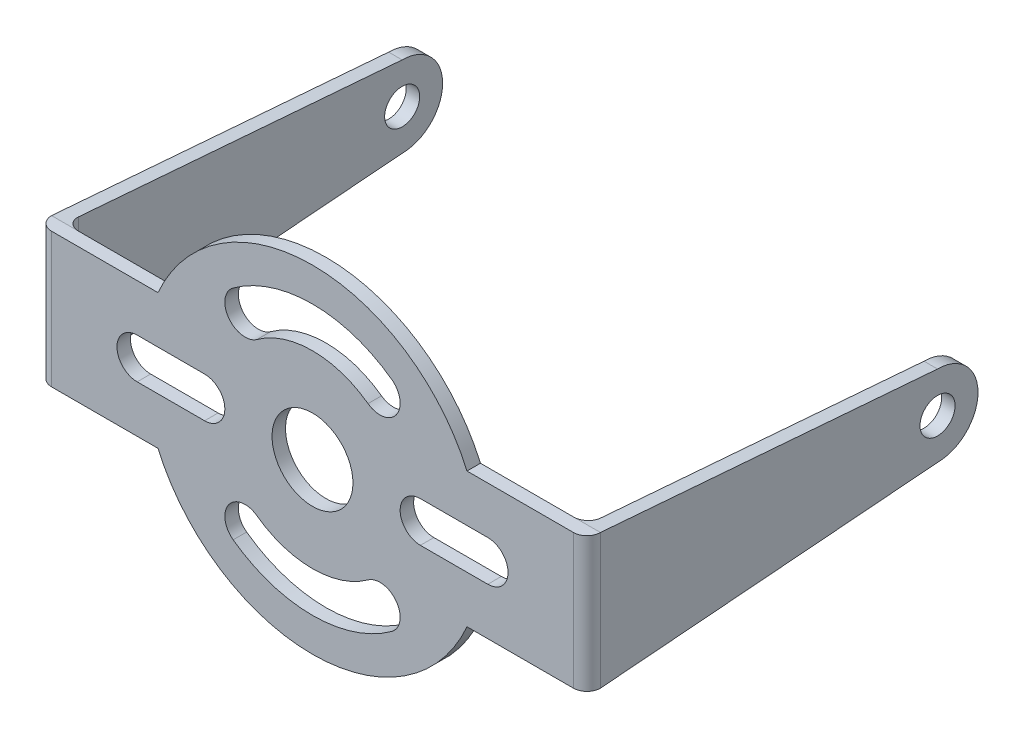
SolidWorks part; units mm, degrees
ref_plane "前视基准面" through (0, 0, 0) normal (0, 0, 1) x (1, 0, 0)
ref_plane "上视基准面" through (0, 0, 0) normal (0, 1, 0) x (1, 0, 0)
ref_plane "右视基准面" through (0, 0, 0) normal (1, 0, 0) x (0, 0, -1)
sketch "Sketch1" plane through (0, 0, 0) normal (0, 0, 1) x (1, 0, 0)
  line L1 (-20.35, 5) -> (20.35, 5)
  line L2 (-20.35, 5) -> (-20.35, -5)
  line L3 (-20.35, -5) -> (20.35, -5)
  line L4 (20.35, 5) -> (20.35, -5)
  line L5 (-20.35, 5) -> (20.35, -5) construction
  line L6 (-20.35, -5) -> (20.35, 5) construction
  circle A0 centre (0, 0) radius 12.5
  circle A1 centre (0, 0) radius 3
  dimension "D1" = 25
  dimension "D2" = 6
  dimension "D3" = 10
  dimension "D4" = 40.7
extrude "Boss-Extrude1" add sketch "Sketch1" along normal blind 1 contours L1 A0 | L1 A0 L3 A1 | A0 L3 L4 L1 | A0 L1 L2 L3 | L3 A0 region at (-16.2483, 0, 0) region at (0, 8.0936, 0) region at (0, 4.7307, 0) region at (16.2483, 0, 0) region at (0, -8.0936, 0)
sketch "Sketch2" plane through (-20.35, 0, 0) normal (-1, 0, 0) x (0, 0, 1)
  line L0 (1, 0) -> (-25, 0) construction
  line L1 (1, 5) -> (1, -5) construction
  line L2 (0, -5) -> (-25, -3)
  line L3 (-25, -3) -> (-25, 3)
  line L4 (-25, 3) -> (0, 5)
  line L5 (0, 5) -> (0, -5)
  circle A0 centre (-25, 0) radius 3
  circle A1 centre (-25, 0) radius 1.3
  line M5 (0, 5) -> (0, -5)
  dimension "D1" = 6
  dimension "D2" = 26
  dimension "D3" = 2.6
extrude "Boss-Extrude2" add sketch "Sketch2" against normal blind 1 contours L5 L0 A0 L2 | L0 L4 A0 M5 | A1 L3 A0 | A0 L0 A1 L3 | L0 A0 L3 A1 region at (-20.35, -1.44, -23.56) region at (-20.35, 2.1001, -10.5252) region at (-20.35, 1.44, -23.56) region at (-20.35, -2.1001, -10.5252) region at (-20.35, 0, -26.44)
ref_plane "Plane1" through (0, 0, 0) normal (-1, 0, 0) x (0, 0, 1)
mirror "Mirror1" about plane through (0, 0, 0) normal (-1, 0, 0) of "Boss-Extrude2"
fillet "Fillet1" radius 1 4 edges at (20.35, 0, 1) (19.35, 0, 0) (-20.35, 0, 1) (-19.35, 0, 0)
sketch "Sketch3" plane through (0, 0, 1) normal (0, 0, 1) x (1, 0, 0)
  line L0 (0, 0) -> (10.5, 0) construction
  line L1 (8, 0) -> (13, 0) construction
  line L2 (8, 1.5) -> (13, 1.5)
  line L3 (8, -1.5) -> (13, -1.5)
  line L4 (0, 0) -> (0, 12.5) construction
  line L5 (-8, 0) -> (-13, 0) construction
  line L6 (-8, 1.5) -> (-13, 1.5)
  line L7 (-8, -1.5) -> (-13, -1.5)
  line L8 (6.5, 0) -> (6.5, -10.6771) construction
  arc A0 (8, 1.5) -> (8, -1.5) centre (8, 0) ccw
  arc A1 (13, -1.5) -> (13, 1.5) centre (13, 0) ccw
  arc A2 (11.4564, 5) -> (-11.4564, 5) centre (0, 0) ccw construction
  arc A3 (-8, 1.5) -> (-8, -1.5) centre (-8, 0) cw
  arc A4 (-13, -1.5) -> (-13, 1.5) centre (-13, 0) cw
  circle A5 centre (0, 0) radius 10
  circle A6 centre (0, 0) radius 7
  arc A7 (-11.4564, -5) -> (11.4564, -5) centre (0, 0) ccw construction
  circle A8 centre (0, 0) radius 8.5
  circle A9 centre (5, -6.8739) radius 1.5
  circle A10 centre (-5, -6.8739) radius 1.5
  circle A11 centre (-5, 6.8739) radius 1.5
  circle A12 centre (5, 6.8739) radius 1.5
  point P5 (10.5, 0)
  point P17 (-10.5, 0)
  dimension "D1" = 13
  dimension "D4" = 20
  dimension "D5" = 3
  dimension "D6" = 1.5
  dimension "D7" = 3
  dimension "D2" = 8
  dimension "D3" = 3
extrude "Cut-Extrude1" cut sketch "Sketch3" against normal blind 1 contours A3 A6 | L6 A8 L7 A3 A6 | A8 L6 A5 L7 | A5 L6 A4 L7 | A0 A6 | L3 A8 L2 A0 A6 | A8 L3 A5 L2 | A5 L3 A1 L2 | A8 A9 | A8 A9 | A8 A10 A5 A9 | A6 A10 A8 A9 | A10 A8 | A10 A8 | A12 A8 | A12 A8 | A8 A12 A5 A11 | A6 A12 A8 A11 | A8 A11 | A8 A11 region at (7.7454, 0, 1) region at (9.2089, 0, 1) region at (6.7817, 0, 1) region at (12.0834, 0, 1) region at (4.6118, 6.3402, 1) region at (5.3601, 7.3689, 1) region at (0, 7.4441, 1) region at (0, 8.9152, 1) region at (0, -7.4441, 1) region at (4.6118, -6.3402, 1) region at (-4.6118, 6.3402, 1) region at (-5.3601, 7.3689, 1) region at (5.3601, -7.3689, 1) region at (-4.6118, -6.3402, 1) region at (0, -8.9152, 1) region at (-7.7454, 0, 1) region at (-6.7817, 0, 1) region at (-12.0834, 0, 1) region at (-9.2089, 0, 1) region at (-5.3601, -7.3689, 1)
